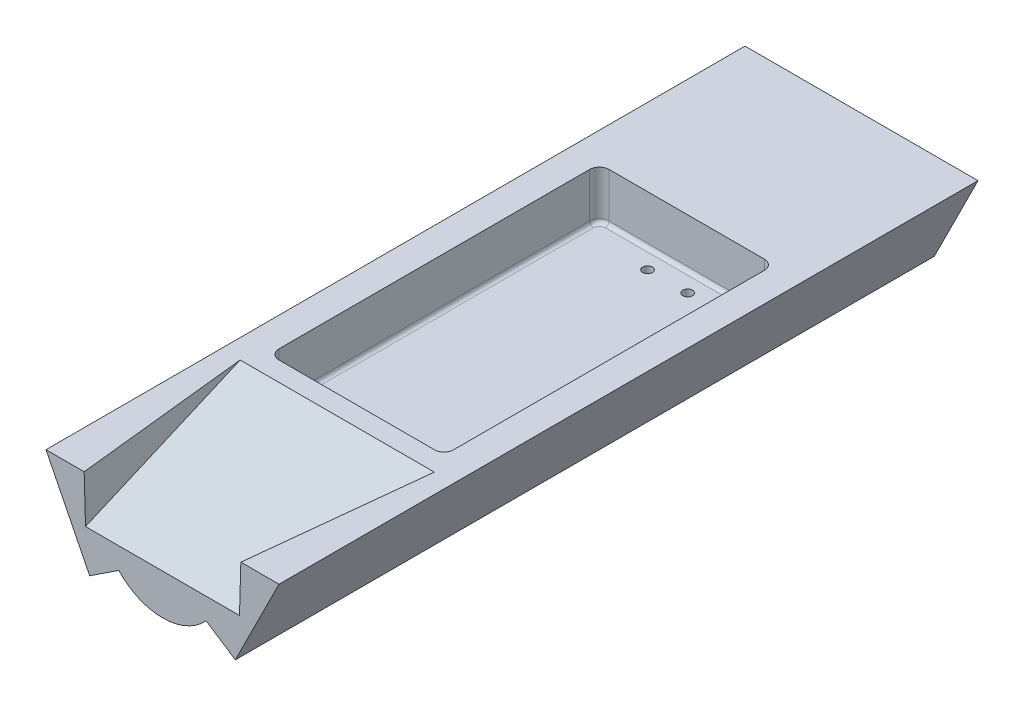
SolidWorks part; units mm, degrees
ref_plane "Front Plane" through (0, 0, 0) normal (0, 0, 1) x (1, 0, 0)
ref_plane "Top Plane" through (0, 0, 0) normal (0, 1, 0) x (1, 0, 0)
ref_plane "Right Plane" through (0, 0, 0) normal (1, 0, 0) x (0, 0, -1)
sketch "Sketch1" plane through (0, 0, 0) normal (0, 0, 1) x (1, 0, 0)
  line L6 (-304.8, 228.6) -> (304.8, 228.6)
  line L9 (0, 0) -> (0, 228.6) construction
  line L15 (-304.8, 228.6) -> (-190.5, 0)
  line L16 (-190.5, 0) -> (-114.3, 50.4)
  line L18 (190.5, 0) -> (304.8, 228.6)
  line L19 (190.5, 0) -> (114.3, 50.4)
  arc A0 (-114.3, 50.4) -> (114.3, 50.4) centre (0, 154.808) ccw
  dimension "D1" = 609.6
  dimension "D2" = 228.6
  dimension "D3" = 228.6
  dimension "D4" = 114.3
  dimension "D5" = 114.3
  dimension "D6" = 76.2
  dimension "D7" = 76.2
extrude "Boss-Extrude2" add sketch "Sketch1" against normal blind 1828.8
sketch "Sketch2" plane through (0, 228.6, 0) normal (0, 1, 0) x (1, 0, 0)
  line L1 (-203.2, 0) -> (203.2, 0)
  line L3 (-254, 457.2) -> (254, 457.2)
  line L6 (-254, 457.2) -> (-203.2, 0)
  line L7 (254, 457.2) -> (203.2, 0)
  line L8 (304.8, 0) -> (-304.8, 0) construction
  dimension "D1" = 508
  dimension "D2" = 457.2
  dimension "D3" = 50.8
  dimension "D4" = 50.8
ref_plane "Plane1" through (0, 98.9867, 26.5234) normal (0, 0.9659, 0.2588) x (1, 0, 0)
sketch "Sketch7" plane through (0, 98.9867, 26.5234) normal (0, 0.9659, 0.2588) x (1, 0, 0)
  line L1 (-254, 500.7873) -> (254, 500.7873)
  line L2 (-254, 500.7873) -> (-196.5534, -16.2318)
  line L3 (254, 500.7873) -> (196.5534, -16.2318)
  line L6 (-196.5534, -16.2318) -> (196.5534, -16.2318)
  dimension "D1" = 508
extrude "Cut-Extrude2" cut sketch "Sketch7" along normal through all
sketch "Sketch8" plane through (0, 228.6, 0) normal (0, 1, 0) x (1, 0, 0)
  line L0 (-304.8, 1828.8) -> (-304.8, 0) construction
  line L1 (-228.6, 508) -> (228.6, 508)
  line L2 (-228.6, 508) -> (-228.6, 1371.6)
  line L3 (-228.6, 1371.6) -> (228.6, 1371.6)
  line L4 (228.6, 508) -> (228.6, 1371.6)
  line L5 (254, 457.2) -> (-254, 457.2) construction
  dimension "D1" = 457.2
  dimension "D2" = 863.6
  dimension "D3" = 76.2
  dimension "D4" = 50.8
extrude "Cut-Extrude5" cut sketch "Sketch8" against normal blind 127
fillet "Fillet1" radius 10 4 edges at (0, 101.6, -1371.6) (228.6, 101.6, -939.8) (0, 101.6, -508) (-228.6, 101.6, -939.8)
fillet "Fillet2" radius 25.4 8 edges at (225.6711, 104.5289, -510.9289) (-225.6711, 104.5289, -510.9289) (-228.6, 170.1, -508) (228.6, 170.1, -508) (-225.6711, 104.5289, -1368.6711) (225.6711, 104.5289, -1368.6711) (228.6, 170.1, -1371.6) (-228.6, 170.1, -1371.6)
sketch "Sketch9" plane through (0, 101.6, 0) normal (0, 1, 0) x (1, 0, 0)
  line L0 (0, 1371.6) -> (0, 508) construction
  line L1 (203.2, 1371.6) -> (-203.2, 1371.6) construction
  line L2 (-203.2, 508) -> (203.2, 508) construction
  circle A0 centre (-52.5, 1321.6) radius 12.7
  circle A1 centre (52.5, 1321.6) radius 12.7
  circle A2 centre (0, 571.6) radius 10
  point P12 (0, 0)
  dimension "D1" = 25.4
  dimension "D3" = 50
  dimension "D4" = 20
  dimension "D5" = 750
  dimension "D2" = 52.5
extrude "Cut-Extrude6" cut sketch "Sketch9" against normal through all
